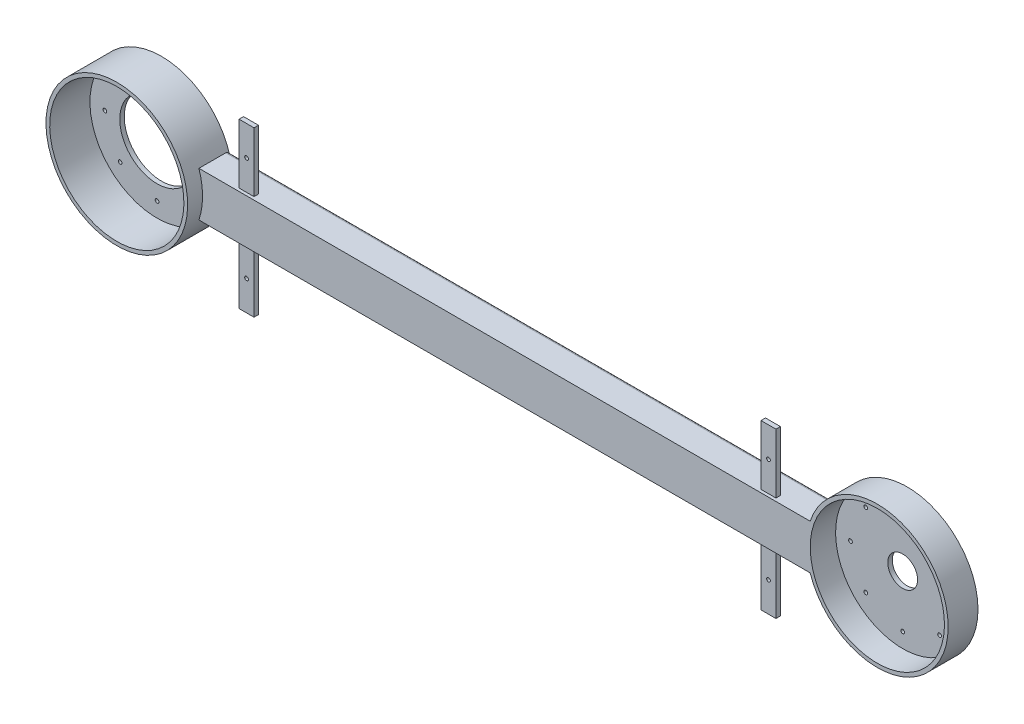
SolidWorks part; units mm, degrees
note: The reader was unsure of these and kept them because the rebuilt part matched: shared geometry of "Sketch5<3>", "Sketch5<4>", "Sketch6<3>", "Sketch6<4>".
ref_plane "Front Plane" through (0, 0, 0) normal (0, 0, 1) x (1, 0, 0)
ref_plane "Top Plane" through (0, 0, 0) normal (0, 1, 0) x (1, 0, 0)
ref_plane "Right Plane" through (0, 0, 0) normal (1, 0, 0) x (0, 0, -1)
sketch "Sketch1" plane through (0, 0, 0) normal (1, 0, 0) x (0, 0, -1)
  line L0 (-8, 15) -> (-10, 15)
  line L1 (8, 15) -> (-8, 15)
  line L2 (10, 13) -> (10, -13)
  line L3 (8, -15) -> (-8, -15)
  line L4 (-10, 13) -> (-10, -13)
  line L5 (10, 15) -> (-10, -15) construction
  line L6 (10, -15) -> (-10, 15) construction
  line L11 (-7, 14) -> (7, 14)
  line L12 (-9, 12) -> (-9, -12)
  line L13 (-7, -14) -> (7, -14)
  line L14 (9, 12) -> (9, -12)
  line L15 (-9, 14) -> (9, -14) construction
  line L16 (-9, -14) -> (9, 14) construction
  line L17 (-10, 15) -> (-10, 13)
  line L18 (-7, 14) -> (-9, 14)
  line L19 (-9, 14) -> (-9, 12)
  line L20 (-10, -13) -> (-10, -15)
  line L21 (-10, -15) -> (-8, -15)
  line L22 (-9, -12) -> (-9, -14)
  line L23 (-9, -14) -> (-7, -14)
  arc A0 (10, 13) -> (8, 15) centre (8, 13) ccw
  arc A1 (8, -15) -> (10, -13) centre (8, -13) ccw
  arc A4 (7, -14) -> (9, -12) centre (7, -12) ccw
  arc A6 (9, 12) -> (7, 14) centre (7, 12) ccw
  point P0 (0, 0)
  point P18 (0, 0)
  dimension "D3" = 2
  dimension "D6" = 2
  dimension "D1" = 20
  dimension "D2" = 30
  dimension "D4" = 18
  dimension "D5" = 28
extrude "Boss-Extrude1" add sketch "Sketch1" along normal blind 500
ref_plane "Plane2" through (0, 0, -10) normal (0, 0, -1) x (-1, 0, 0)
sketch "Sketch5" plane through (0, 0, -10) normal (0, 0, -1) x (-1, 0, 0)
  line L0 (0, 0) -> (0, -47.5) construction
  line L1 (0, -47.5) -> (0, 47.5) construction
  line L2 (0, 47.5) -> (0, 0) construction
  line L3 (0, 0) -> (47.5, 0) construction
  line L4 (47.5, 0) -> (-47.5, 0) construction
  line L5 (-47.5, 0) -> (0, 0) construction
  line L6 (0, 0) -> (33.5876, 33.5876) construction
  line L7 (33.5876, 33.5876) -> (-33.5876, -33.5876) construction
  line L8 (-33.5876, -33.5876) -> (0, 0) construction
  line L9 (0, 0) -> (33.5876, -33.5876) construction
  line L10 (33.5876, -33.5876) -> (-33.5876, 33.5876) construction
  circle A0 centre (0, 0) radius 45
  circle A1 centre (0, 0) radius 47.5
  circle A2 centre (0, 0) radius 25
  circle A3 centre (0, 0) radius 35
  point P14 (-24.7487, 24.7487)
  point P15 (-24.7487, -24.7487)
  point P16 (24.7487, -24.7487)
  point P17 (24.7487, 24.7487)
  point P18 (0, 35)
  point P19 (35, 0)
  point P20 (-35, 0)
  point P21 (0, -35)
  dimension "D1" = 90
  dimension "D2" = 95
  dimension "D3" = 50
extrude "Boss-Extrude2" add sketch "Sketch5" against normal blind 30 separate body contours A1 A0
extrude "Cut-Extrude1" cut sketch "Sketch5<3>" against normal blind 50 contours A0 A3 | A3 A2 | A2
sketch "Sketch5<3>" plane through (0, 0, -10) normal (0, 0, -1) x (-1, 0, 0) same geometry as "Sketch5"
extrude "Boss-Extrude3" add sketch "Sketch5<4>" against normal blind 3 contours A3 A2 | A0 A3
sketch "Sketch5<4>" plane through (0, 0, -10) normal (0, 0, -1) x (-1, 0, 0) same geometry as "Sketch5"
sketch "Sketch6" plane through (0, 0, -10) normal (0, 0, -1) x (-1, 0, 0)
  line L0 (0, 0) -> (-593.5989, 0) construction
  line L1 (-500, -13) -> (-500, 13) construction
  circle A0 centre (-500, 0) radius 45
  circle A1 centre (-500, 0) radius 10
  circle A2 centre (-500, 0) radius 47.5
  point P3 (-500, 0)
  dimension "D1" = 20
  dimension "D2" = 90
  dimension "D3" = 95
extrude "Boss-Extrude4" add sketch "Sketch6" against normal blind 20 contours L0 A2 A0 | A2 L0 A0
extrude "Cut-Extrude2" cut sketch "Sketch6<3>" against normal blind 60 contours A0 L0 A1 | L0 A0 A1 | L0 A1 | A1 L0
sketch "Sketch6<3>" plane through (0, 0, -10) normal (0, 0, -1) x (-1, 0, 0) same geometry as "Sketch6"
extrude "Boss-Extrude5" add sketch "Sketch6<4>" against normal blind 3 contours L0 A0 A1 | A0 L0 A1
sketch "Sketch6<4>" plane through (0, 0, -10) normal (0, 0, -1) x (-1, 0, 0) same geometry as "Sketch6"
ref_plane "Plane3" through (0, 15, 0) normal (0, 1, 0) x (1, 0, 0)
ref_plane "Plane4" through (0, 0, 5) normal (0, 0, -1) x (-1, 0, 0)
sketch "Sketch8" plane through (0, 0, 5) normal (0, 0, -1) x (-1, 0, 0)
  line L0 (0, 0) -> (-500, 0) construction
  line L1 (-75, 0) -> (-75, 57.0142) construction
  line L2 (-75, 57.0142) -> (-75, -67.9474) construction
  line L3 (-425, 0) -> (-425, 59.8607) construction
  line L4 (-425, 59.8607) -> (-425, -73.7117) construction
  line L5 (-454.9306, -15) -> (-45.0694, -15) construction
  line L7 (9.9, 15) -> (-9.9, 15) construction
  line L8 (-70, 55) -> (-80, 55)
  line L9 (-70, 55) -> (-70, 15)
  line L10 (-70, 15) -> (-80, 15)
  line L11 (-80, 55) -> (-80, 15)
  line L12 (-70, 55) -> (-80, 15) construction
  line L13 (-70, 15) -> (-80, 55) construction
  line L15 (-80, -55) -> (-70, -55)
  line L16 (-80, -55) -> (-80, -15)
  line L17 (-80, -15) -> (-70, -15)
  line L18 (-70, -55) -> (-70, -15)
  line L19 (-80, -55) -> (-70, -15) construction
  line L20 (-80, -15) -> (-70, -55) construction
  line L22 (-420, 55) -> (-430, 55)
  line L23 (-420, 55) -> (-420, 15)
  line L24 (-420, 15) -> (-430, 15)
  line L25 (-430, 55) -> (-430, 15)
  line L26 (-420, 55) -> (-430, 15) construction
  line L27 (-420, 15) -> (-430, 55) construction
  line L28 (-420, -55) -> (-430, -55)
  line L29 (-420, -55) -> (-420, -15)
  line L30 (-420, -15) -> (-430, -15)
  line L31 (-430, -55) -> (-430, -15)
  line L32 (-420, -55) -> (-430, -15) construction
  line L33 (-420, -15) -> (-430, -55) construction
  point P4 (-75, 0)
  point P7 (-425, 0)
  point P11 (-425, 35)
  point P13 (-425, -35)
  point P14 (-75, 35)
  point P15 (-75, -35)
  point P18 (-75, -35)
  point P19 (-75, 35)
  point P28 (-430, -15)
  point P30 (-425, 35)
  point P35 (-425, -35)
  point P40 (0, 0)
  point P41 (-70, -15)
  point P44 (0, 0)
  dimension "D1" = 75
  dimension "D2" = 75
  dimension "D3" = 35
  dimension "D4" = 35
  dimension "D5" = 35
  dimension "D6" = 35
  dimension "D7" = 10
  dimension "D8" = 10
  dimension "D9" = 10
  dimension "D10" = 10
extrude "Boss-Extrude6" add sketch "Sketch8" against normal blind 3 contours L15 L18 L17 L16 | L8 L11 L10 L9 | L22 L25 L24 L23 | L31 L28 L29 L30
hole_wizard "M3 Tapped Hole1" positions "Sketch9" profile "Sketch10" tap size "M3" standard "ISO"
sketch "Sketch9" plane through (0, 0, 5) normal (0, 0, -1) x (-1, 0, 0)
  line L0 (0, 0) -> (134.6199, 0) construction
  line L1 (-500, 0) -> (378.626, 0) construction
  point P0 (-75, 35)
  point P2 (-75, -35)
  point P4 (-425, 35)
  point P6 (-425, -35)
  point P21 (-75, 0)
  point P28 (-425, 0)
  dimension "D1" = 75
  dimension "D2" = 35
  dimension "D3" = 35
  dimension "D4" = 75
sketch "Sketch10" plane through (75, 35, 5) normal (1, 0, 0) x (0, 1, 0)
  line L0 (0, 0) -> (0, 3.7501)
  line L1 (0, 3.7501) -> (1.25, 2.999)
  line L2 (1.25, 2.999) -> (1.25, 0.275)
  line L3 (1.25, 0.275) -> (1.525, 0)
  line L5 (1.525, 0) -> (0, 0)
  line L6 (-1.25, 0.275) -> (-1.525, 0) construction
  line L10 (0, 3.7501) -> (-1.25, 2.999) construction
  line L11 (0, -6.35) -> (0, 107.95) construction
  dimension "Tap Drill Dia." = 2.5
  dimension "Tap Drill Depth" = 2.999
  dimension "Near C'Sink Dia." = 3.05
  dimension "Near C'Sink Angle" = 90
  dimension "Drill Angle" = 118
cosmetic thread "Hole Thread1" parameters "D1"=6, "D2"=3
cosmetic thread "Hole Thread2" parameters "D1"=6, "D2"=3
cosmetic thread "Hole Thread3" parameters "D1"=6, "D2"=3
cosmetic thread "Hole Thread4" parameters "D1"=6, "D2"=3
hole_wizard "M3 Tapped Hole2" positions "Sketch11" profile "Sketch12" tap size "M3" standard "ISO"
sketch "Sketch11" plane through (0, 0, -10) normal (0, 0, -1) x (-1, 0, 0)
  line L0 (50.0578, 0) -> (0, 0) construction
  line L1 (0, 0) -> (-604.0803, 0) construction
  line L4 (-500, 0) -> (-500, -105.5521) construction
  line L5 (-500, -105.5521) -> (-500, 58.8934) construction
  line L8 (0, 0) -> (0, -72.8888) construction
  line L11 (0, 0) -> (0, 56.8832) construction
  line L14 (0, 0) -> (-33.5876, -33.5876) construction
  line L15 (-33.5876, -33.5876) -> (33.5876, 33.5876) construction
  line L16 (33.5876, 33.5876) -> (0, 0) construction
  line L17 (0, 0) -> (33.5876, -33.5876) construction
  line L18 (33.5876, -33.5876) -> (-33.5876, 33.5876) construction
  line L19 (-500, 0) -> (-533.5876, -33.5876) construction
  line L20 (-533.5876, -33.5876) -> (-466.4124, 33.5876) construction
  line L21 (-466.4124, 33.5876) -> (-500, 0) construction
  line L22 (-500, 0) -> (-533.5876, 33.5876) construction
  line L23 (-533.5876, 33.5876) -> (-466.4124, -33.5876) construction
  arc A0 (-45.6864, -13) -> (-45.6864, 13) centre (0, 0) ccw construction
  arc A1 (-454.3136, 13) -> (-454.3136, -13) centre (-500, 0) ccw construction
  circle A2 centre (-500, 0) radius 35
  circle A3 centre (0, 0) radius 35
  point P0 (24.7487, -24.7487)
  point P2 (0, -35)
  point P4 (0, 35)
  point P6 (35, 0)
  point P8 (-35, 0)
  point P10 (-24.7487, 24.7487)
  point P12 (-24.7487, -24.7487)
  point P14 (24.7487, 24.7487)
  point P16 (-500, 35)
  point P18 (-524.7487, 24.7487)
  point P20 (-535, 0)
  point P22 (-465, 0)
  point P24 (-475.2513, 24.7487)
  point P26 (-524.7487, -24.7487)
  point P28 (-500, -35)
  point P30 (-475.2513, -24.7487)
  dimension "D1" = 70
sketch "Sketch12" plane through (-24.7487, -24.7487, -10) normal (1, 0, 0) x (0, 1, 0)
  line L0 (0, 0) -> (0, 3.7501)
  line L1 (0, 3.7501) -> (1.25, 2.999)
  line L2 (1.25, 2.999) -> (1.25, 0.275)
  line L3 (1.25, 0.275) -> (1.525, 0)
  line L5 (1.525, 0) -> (0, 0)
  line L6 (-1.25, 0.275) -> (-1.525, 0) construction
  line L10 (0, 3.7501) -> (-1.25, 2.999) construction
  line L11 (0, -6.35) -> (0, 107.95) construction
  dimension "Tap Drill Dia." = 2.5
  dimension "Tap Drill Depth" = 2.999
  dimension "Near C'Sink Dia." = 3.05
  dimension "Near C'Sink Angle" = 90
  dimension "Drill Angle" = 118
cosmetic thread "Hole Thread5" parameters "D1"=6, "D2"=3
cosmetic thread "Hole Thread6" parameters "D1"=6, "D2"=3
cosmetic thread "Hole Thread7" parameters "D1"=6, "D2"=3
cosmetic thread "Hole Thread8" parameters "D1"=6, "D2"=3
cosmetic thread "Hole Thread9" parameters "D1"=6, "D2"=3
cosmetic thread "Hole Thread10" parameters "D1"=6, "D2"=3
cosmetic thread "Hole Thread11" parameters "D1"=6, "D2"=3
cosmetic thread "Hole Thread12" parameters "D1"=6, "D2"=3
cosmetic thread "Hole Thread13" parameters "D1"=6, "D2"=3
cosmetic thread "Hole Thread14" parameters "D1"=6, "D2"=3
cosmetic thread "Hole Thread15" parameters "D1"=6, "D2"=3
cosmetic thread "Hole Thread16" parameters "D1"=6, "D2"=3
cosmetic thread "Hole Thread17" parameters "D1"=6, "D2"=3
cosmetic thread "Hole Thread18" parameters "D1"=6, "D2"=3
cosmetic thread "Hole Thread19" parameters "D1"=6, "D2"=3
cosmetic thread "Hole Thread20" parameters "D1"=6, "D2"=3
sketch "Sketch3" plane through (0, 0, 0) normal (0, 0, 1) x (1, 0, 0)
  circle A0 centre (0, 0) radius 30
  circle A1 centre (0, 0) radius 28
  circle A2 centre (0, 0) radius 25
  dimension "D1" = 60
  dimension "D2" = 56
  dimension "D3" = 50
